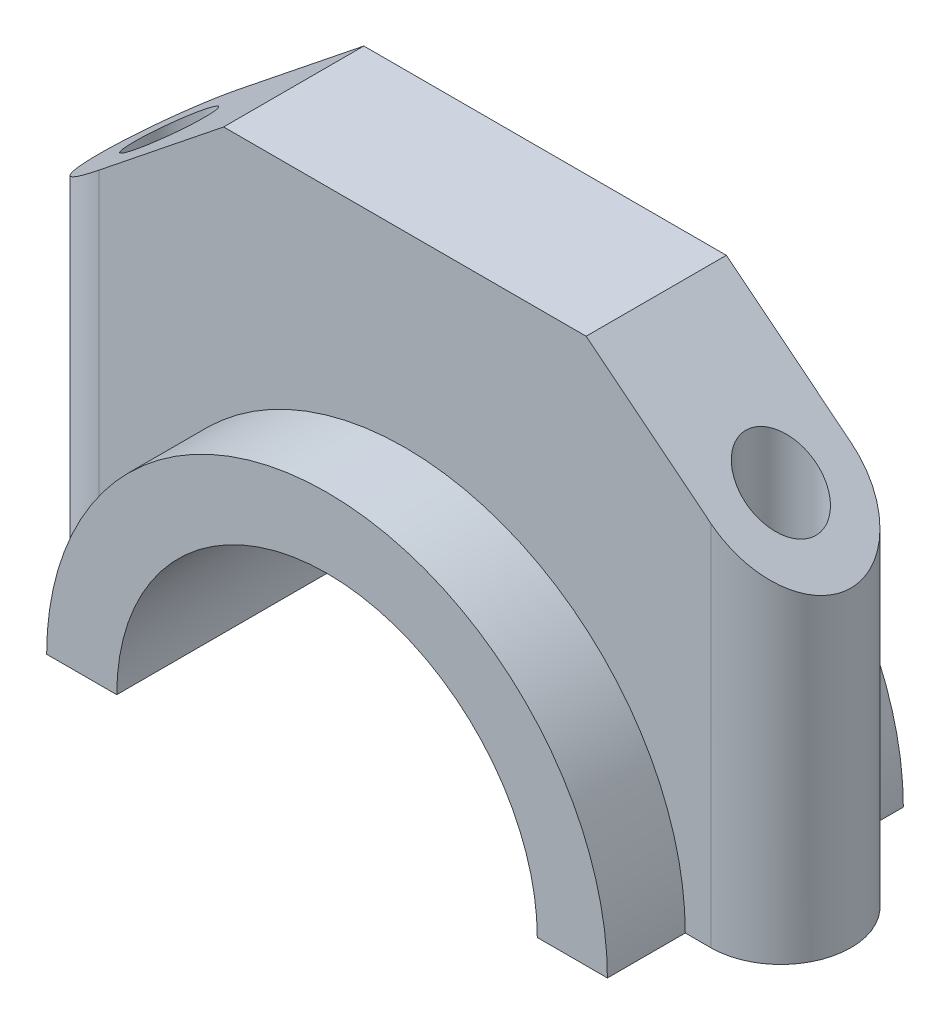
SolidWorks part; units mm, degrees
ref_plane "Front Plane" through (0, 0, 0) normal (0, 0, 1) x (1, 0, 0)
ref_plane "Top Plane" through (0, 0, 0) normal (0, 1, 0) x (1, 0, 0)
ref_plane "Right Plane" through (0, 0, 0) normal (1, 0, 0) x (0, 0, -1)
sketch "Sketch1" plane through (0, 0, 0) normal (0, 0, 1) x (1, 0, 0)
  line L0 (-36, 0) -> (36, 0)
  arc A0 (27, 0) -> (-27, 0) centre (0, 0) ccw
  arc A1 (36, 0) -> (-36, 0) centre (0, 0) ccw
  dimension "D1" = 54
  dimension "D2" = 72
extrude "Boss-Extrude1" add sketch "Sketch1" along normal blind 38 contours L0 A1 A0 region at (0, 35.195, 0)
ref_plane "Plane1" through (0, 60, 0) normal (0, -1, 0) x (-1, 0, 0)
sketch "Sketch2" plane through (0, 60, 0) normal (0, -1, 0) x (-1, 0, 0)
  line L0 (-39.2728, -19) -> (39.2728, -19) construction
  line L1 (-39.2728, -10) -> (39.2728, -10)
  line L2 (-39.2728, -28) -> (39.2728, -28)
  line L3 (27, 0) -> (-27, 0) construction
  arc A0 (-39.2728, -10) -> (-39.2728, -28) centre (-39.2728, -19) ccw
  arc A1 (39.2728, -28) -> (39.2728, -10) centre (39.2728, -19) ccw
  point P2 (0, -19)
  point P7 (0, 0)
  dimension "D2" = 9
  dimension "D1" = 19
extrude "Boss-Extrude2" add sketch "Sketch2" along normal up to surface (60 mm away) up to face at (31.5, 0, 19)
sketch "Sketch3" plane through (0, 0, 28) normal (0, 0, 1) x (1, 0, 0)
  circle A0 centre (0, 0) radius 27
extrude "Cut-Extrude1" cut sketch "Sketch3" against normal blind 38
sketch "Sketch4" plane through (0, 60, 0) normal (0, 1, 0) x (1, 0, 0)
  circle A0 centre (-39.2728, -19) radius 4.5
  dimension "D1" = 9
extrude "Cut-Extrude2" cut sketch "Sketch4" against normal blind 64
mirror "Mirror1" about plane through (0, 0, 0) normal (1, 0, 0) of "Cut-Extrude2"
sketch "Sketch5" plane through (0, 0, 0) normal (0, 0, 1) x (1, 0, 0)
  line L0 (-23.2728, 60) -> (-48.2728, 40)
  line L1 (39.2728, 60) -> (-39.2728, 60) construction
  line L2 (-48.2728, 60) -> (-48.2728, 0) construction
  line L3 (-11.7, 60) -> (11.7, 60) construction
  dimension "D1" = 20
  dimension "D2" = 25
sketch "Sketch6" plane through (0, 0, 28) normal (0, 0, 1) x (1, 0, 0)
  line L0 (-23.2728, 60) -> (-48.2728, 40)
  line L1 (-48.2728, 40) -> (-48.2728, 60)
  line L2 (-48.2728, 60) -> (-48.2728, 0) construction
  line L3 (-11.7, 60) -> (11.7, 60) construction
  line L4 (-48.2728, 60) -> (-23.2728, 60)
  line L5 (-39.2728, 0) -> (-36, 0)
  line L6 (36, 0) -> (39.2728, 0)
  line L7 (39.2728, 0) -> (39.2728, 60)
  line L8 (39.2728, 60) -> (-39.2728, 60)
  line L9 (-39.2728, 60) -> (-39.2728, 0)
  line L10 (-39.2728, 0) -> (-36, 0)
  line L11 (36, 0) -> (39.2728, 0)
  line L12 (39.2728, 0) -> (39.2728, 60)
  line L13 (39.2728, 60) -> (-39.2728, 60)
  line L14 (-39.2728, 60) -> (-39.2728, 0)
  arc A1 (36, 0) -> (-36, 0) centre (0, 0) ccw
  arc A2 (36, 0) -> (-36, 0) centre (0, 0) ccw
  line M11 (39.2728, 60) -> (-39.2728, 60)
  line M12 (-39.2728, 60) -> (-39.2728, 0)
  dimension "D1" = 0
extrude "Cut-Extrude3" cut sketch "Sketch6" against normal blind 64 contours L4 L1 L0 M12 | L0 M11 M12 region at (-33.9395, 55.7333, 28) region at (-44.1021, 51.6683, 28)
mirror "Mirror2" about plane through (0, 0, 0) normal (1, 0, 0) of "Cut-Extrude3"
